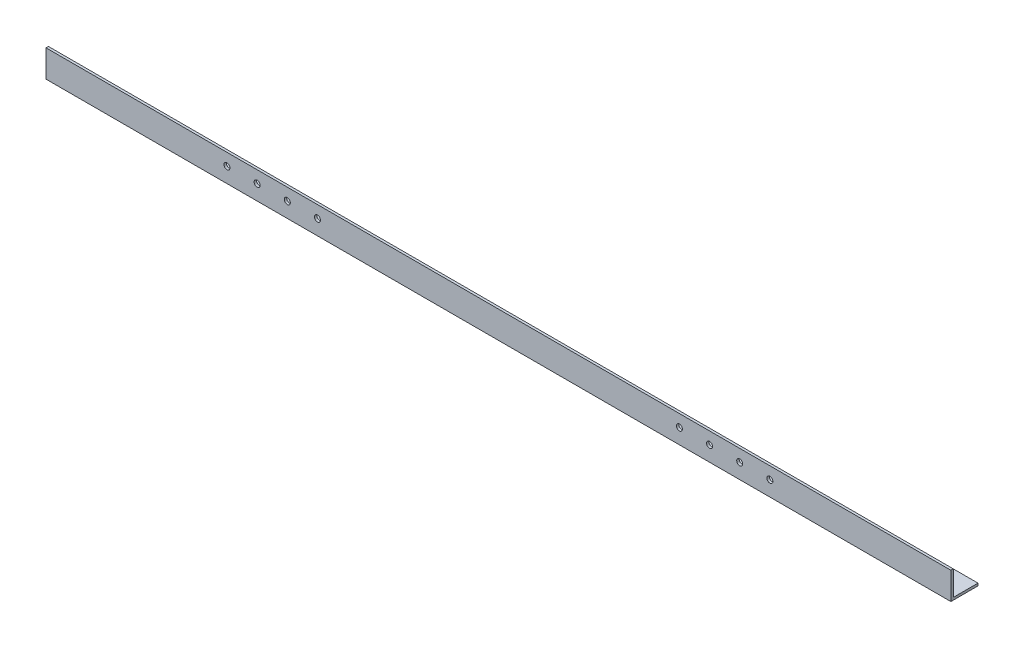
SolidWorks part; units mm, degrees
ref_plane "Спереди" through (0, 0, 0) normal (0, 0, 1) x (1, 0, 0)
ref_plane "Сверху" through (0, 0, 0) normal (0, 1, 0) x (1, 0, 0)
ref_plane "Справа" through (0, 0, 0) normal (1, 0, 0) x (0, 0, -1)
sketch "Эскиз1" plane through (0, 0, 0) normal (1, 0, 0) x (0, 0, -1)
  line L0 (0, 0) -> (0, 45)
  line L1 (0, 0) -> (45, 0)
  dimension "D1" = 45
  dimension "D2" = 45
extrude "Вытянуть-Тонкостенный1" add sketch "Эскиз1" along normal blind 1500 thin thin type one direction reverse wall 4
sketch "Эскиз2" plane through (0, 0, 0) normal (0, 0, 1) x (1, 0, 0)
  line L0 (750, 45) -> (750, -21.7338) construction
  line L1 (1500, 45) -> (0, 45) construction
  circle A0 centre (300, 25) radius 5
  circle A1 centre (350, 25) radius 5
  circle A2 centre (400, 25) radius 5
  circle A3 centre (450, 25) radius 5
  circle A4 centre (1050, 25) radius 5
  circle A5 centre (1100, 25) radius 5
  circle A6 centre (1150, 25) radius 5
  circle A7 centre (1200, 25) radius 5
  dimension "D1" = 4
extrude "Вырез-Вытянуть1" cut sketch "Эскиз2" against normal through all
